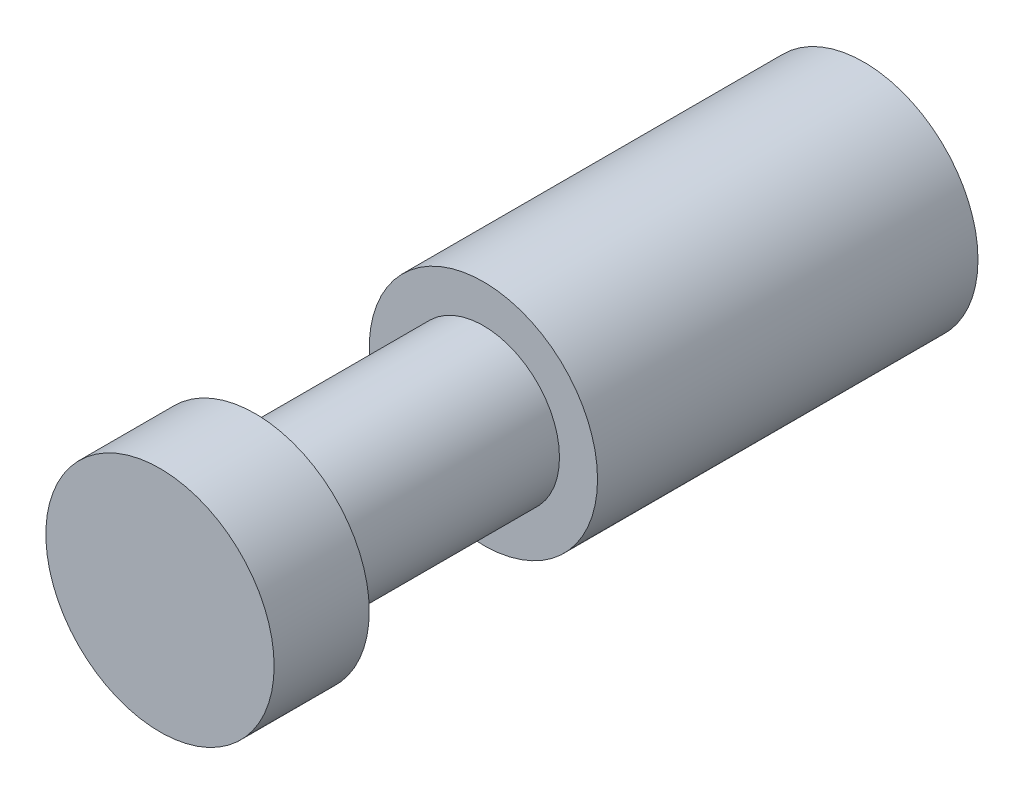
SolidWorks part; units mm, degrees
ref_plane "Front Plane" through (0, 0, 0) normal (0, 0, 1) x (1, 0, 0)
ref_plane "Top Plane" through (0, 0, 0) normal (0, 1, 0) x (1, 0, 0)
ref_plane "Right Plane" through (0, 0, 0) normal (1, 0, 0) x (0, 0, -1)
sketch "Sketch1" plane through (0, 0, 0) normal (0, 0, 1) x (1, 0, 0)
  circle A0 centre (0, 0) radius 4.4
  circle A1 centre (0, 0) radius 6
  dimension "D1" = 8.8
  dimension "D2" = 12
extrude "Boss-Extrude1" add sketch "Sketch1" along normal blind 12
sketch "Sketch2" plane through (0, 0, 12) normal (0, 0, 1) x (1, 0, 0)
  circle A0 centre (0, 0) radius 6
  circle A1 centre (0, 0) radius 6 construction
  dimension "D1" = 0
extrude "Boss-Extrude2" add sketch "Sketch2" along normal blind 2
sketch "Sketch3" plane through (0, 0, 14) normal (0, 0, 1) x (1, 0, 0)
  circle A0 centre (0, 0) radius 4
  dimension "D1" = 8
extrude "Boss-Extrude3" add sketch "Sketch3" along normal blind 18
sketch "Sketch4" plane through (0, 0, 32) normal (0, 0, 1) x (1, 0, 0)
  circle A0 centre (0, 0) radius 6
  dimension "D1" = 12
extrude "Boss-Extrude4" add sketch "Sketch4" along normal blind 5
sketch "Sketch5" plane through (0, 0, 14) normal (0, 0, 1) x (1, 0, 0)
  circle A0 centre (0, 0) radius 6
  circle A1 centre (0, 0) radius 6 construction
extrude "Boss-Extrude5" add sketch "Sketch5" along normal blind 6
